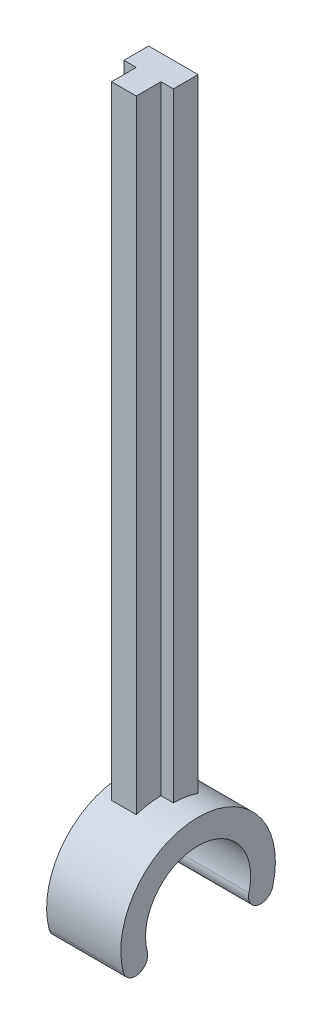
SolidWorks part; units mm, degrees
ref_plane "Front" through (0, 0, 0) normal (0, 0, 1) x (1, 0, 0)
ref_plane "Top" through (0, 0, 0) normal (0, 1, 0) x (1, 0, 0)
ref_plane "Right" through (0, 0, 0) normal (1, 0, 0) x (0, 0, -1)
sketch "Sketch1" plane through (0, 0, 0) normal (1, 0, 0) x (0, 0, -1)
  line L0 (0, 0) -> (-6.25, 0)
  line L1 (0, 0) -> (-6.037, -1.6176)
  line L2 (0, 50) -> (0, -50) construction
  line L3 (0, 0) -> (6.037, -1.6176)
  line L4 (-6.037, -1.6176) -> (-5.0711, -1.3588)
  circle A0 centre (0, 0) radius 4.25
  circle A1 centre (0, 0) radius 6.25
  arc A2 (-6.037, -1.6176) -> (-4.1052, -1.1) centre (-5.0711, -1.3588) ccw
  arc A3 (6.037, -1.6176) -> (4.1052, -1.1) centre (5.0711, -1.3588) cw
  dimension "D1" = 15
  dimension "D3" = 12.5
  dimension "D4" = 8.5
  dimension "D2" = 1
extrude "Boss-Extrude1" add sketch "Sketch1" against normal blind 2 and the other way blind 4 contours L3 A1 L0 A0 | A3 L3 | L0 A1 L1 A0 | L1 A2 region at (0, -0.6916, 5.253) region at (0, 0.1477, 5.25) region at (0, -1.7688, 4.9613) region at (0, -1.7688, -4.9613)
sketch "Sketch2" plane through (0, 0, 0) normal (1, 0, 0) x (0, 0, -1)
  line L0 (0, 0) -> (0, 6.25)
  line L1 (0, 6.25) -> (0, 4.25)
  line L2 (0, 4.25) -> (-2, 4.25)
  line L3 (0, 56.25) -> (0, 4.25)
  line L4 (-2, 4.25) -> (2, 4.25)
  line L5 (-2, 4.25) -> (-2, 56.25)
  line L6 (-2, 56.25) -> (2, 56.25)
  line L7 (2, 4.25) -> (2, 56.25)
  arc A0 (6.037, -1.6176) -> (-6.037, -1.6176) centre (0, 0) ccw construction
  dimension "D1" = 2
  dimension "D2" = 2
  dimension "D3" = 4
  dimension "D4" = 52
extrude "Boss-Extrude2" add sketch "Sketch2" along normal blind 2 and the other way blind 2 contours L4 L7 L6 L3 L0 region at (0, 30.25, -1)
sketch "Sketch3" plane through (0, 0, 0) normal (1, 0, 0) x (0, 0, -1)
  line L1 (0, 56.25) -> (-2, 56.25)
  line L2 (0, 56.25) -> (0, 4.25)
  line L3 (0, 4.25) -> (-2, 4.25)
  line L4 (-2, 56.25) -> (-2, 4.25)
  dimension "D1" = 52
  dimension "D2" = 2
extrude "Boss-Extrude3" add sketch "Sketch3" along normal blind 1 and the other way blind 1
